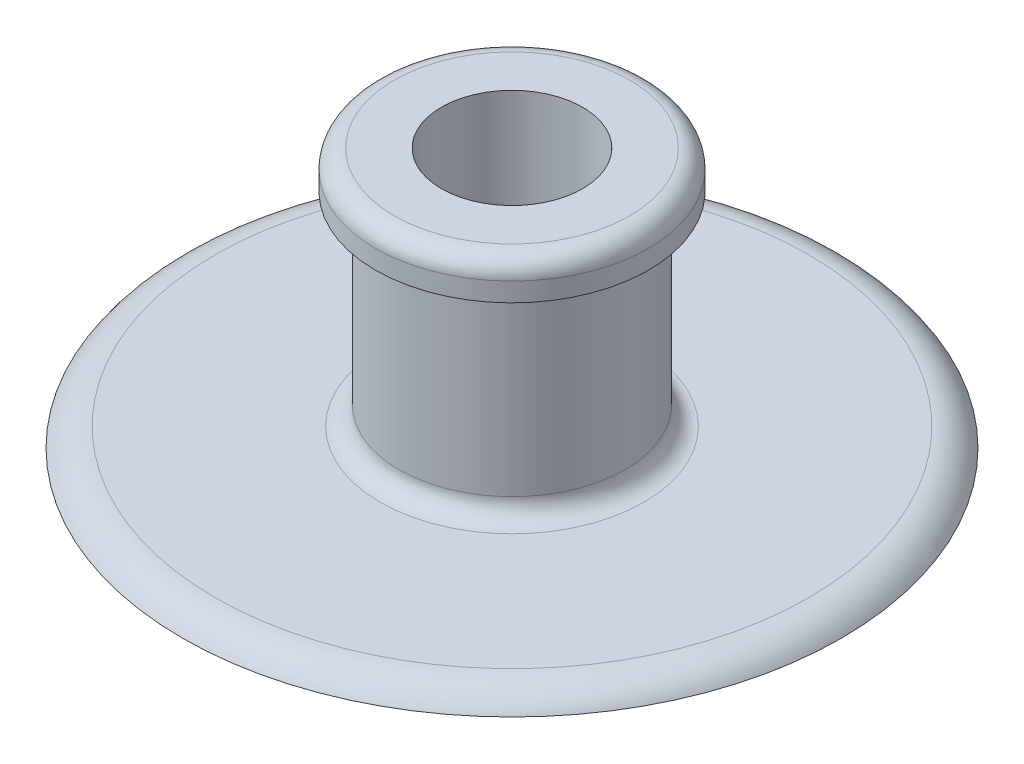
SolidWorks part; units mm, degrees
ref_plane "Front Plane" through (0, 0, 0) normal (0, 0, 1) x (1, 0, 0)
ref_plane "Top Plane" through (0, 0, 0) normal (0, 1, 0) x (1, 0, 0)
ref_plane "Right Plane" through (0, 0, 0) normal (1, 0, 0) x (0, 0, -1)
sketch "Sketch1" plane through (0, 0, 0) normal (0, 1, 0) x (1, 0, 0)
  line L0 (0, 38.0814) -> (0, -33.9224) construction
  line L1 (-52.7681, 0) -> (49.2589, 0) construction
  circle A0 centre (0, 0) radius 22.225
  dimension "D1" = 44.45
extrude "Boss-Extrude1" add sketch "Sketch1" along normal blind 1.27
sketch "Sketch2" plane through (0, 1.27, 0) normal (0, 1, 0) x (1, 0, 0)
  line L0 (-23.4085, 0) -> (23.7033, 0) construction
  line L1 (0, 23.1136) -> (0, -24.116) construction
  circle A0 centre (0, 0) radius 7.62
  dimension "D1" = 15.24
extrude "Boss-Extrude2" add sketch "Sketch2" along normal blind 16.256 contours A0
sketch "Sketch3" plane through (0, 17.526, 0) normal (0, 1, 0) x (1, 0, 0)
  line L0 (0, 22.225) -> (0, -22.225) construction
  line L1 (-22.225, 0) -> (22.225, 0) construction
  circle A0 centre (0, 0) radius 4.7625
  circle A1 centre (0, 0) radius 22.225 construction
  dimension "D1" = 9.525
extrude "Cut-Extrude1" cut sketch "Sketch3" against normal through all
fillet "Fillet1" radius 1.27 1 edges at (0, 1.27, 7.62)
sketch "Sketch4" plane through (0, 0, 0) normal (1, 0, 0) x (0, 0, -1)
  line L0 (0, 0) -> (0, 17.526) construction
  line L1 (4.7625, 17.526) -> (-4.7625, 17.526) construction
  line L2 (-7.62, 2.54) -> (7.62, 2.54) construction
  line L3 (-7.62, 17.526) -> (-7.62, 2.54) construction
  line L4 (7.62, 2.54) -> (7.62, 17.526) construction
  line L5 (7.62, 17.526) -> (-7.62, 17.526) construction
  circle A0 centre (0, 2.54) radius 0.508
  dimension "D1" = 1.016
  dimension "D2" = 14.986
extrude "Cut-Extrude2" cut sketch "Sketch4" against normal through all
fillet "Fillet2" radius 2.54 1 edges at (0, 1.27, 22.225)
fillet "Fillet3" radius 2.54 1 edges at (0, 0, 4.7625)
sketch "Sketch5" plane through (0, 0, 0) normal (0, 0, 1) x (1, 0, 0)
  line L0 (0, 19.9166) -> (0, -2.3906) construction
  line L1 (7.62, 17.526) -> (9.2075, 17.526)
  line L2 (9.2075, 17.526) -> (9.2075, 14.986)
  line L3 (9.2075, 14.986) -> (7.62, 14.986)
  line L4 (7.62, 2.54) -> (7.62, 17.526) construction
  line L5 (7.62, 17.526) -> (7.62, 14.986)
  dimension "D1" = 2.54
  dimension "D2" = 1.5875
revolve "Revolve1" add sketch "Sketch5" angle 360 about L0
fillet "Fillet4" radius 1.27 1 edges at (0, 17.526, 9.2075)
